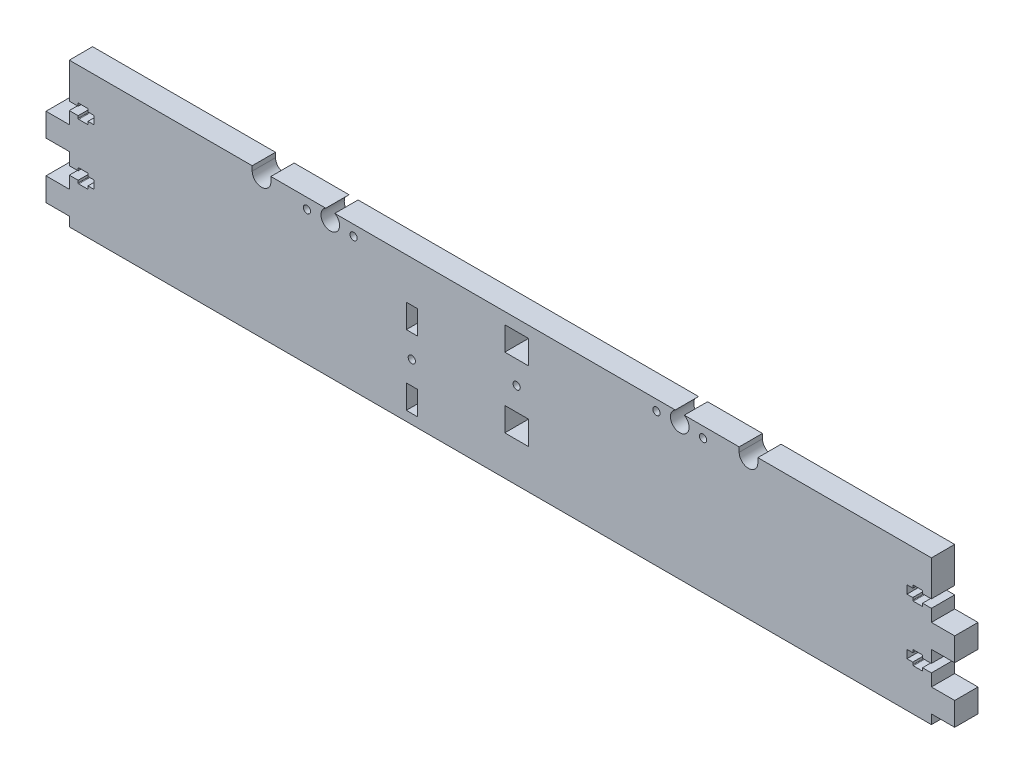
SolidWorks part; units mm, degrees
ref_plane "Front Plane" through (0, 0, 0) normal (0, 0, 1) x (1, 0, 0)
ref_plane "Top Plane" through (0, 0, 0) normal (0, 1, 0) x (1, 0, 0)
ref_plane "Right Plane" through (0, 0, 0) normal (1, 0, 0) x (0, 0, -1)
sketch "Sketch1" plane through (0, 0, 0) normal (0, 0, 1) x (1, 0, 0)
  line L0 (0, 0) -> (-185, 0)
  line L1 (-185, 0) -> (-185, -62) construction
  line L2 (0, -62) -> (-185, -62)
  line L3 (-185, -62) -> (-185, -58)
  line L4 (-185, -58) -> (-195, -58)
  line L5 (-195, -58) -> (-195, -48)
  line L6 (-195, -48) -> (-185, -48)
  line L7 (-185, -48) -> (-185, -34)
  line L8 (-185, -34) -> (-195, -34)
  line L9 (-195, -34) -> (-195, -24)
  line L10 (-195, -24) -> (-185, -24)
  line L11 (0, -62) -> (0, 0)
  line L12 (-185, -24) -> (-185, 0)
  line L13 (-195, -58) -> (-195, -24) construction
  line L14 (-195, -29) -> (-185, -29) construction
  line L15 (-195, -53) -> (-185, -53) construction
  dimension "D1" = 185
  dimension "D2" = 10
  dimension "D3" = 10
  dimension "D4" = 10
  dimension "D5" = 24
  dimension "D6" = 29
  dimension "D7" = 62
extrude "MainBody" add sketch "Sketch1" along normal blind 10
sketch "Sketch3" plane through (0, 0, 10) normal (0, 0, 1) x (1, 0, 0)
  line L0 (-185, -17) -> (-174.5, -17) construction
  line L1 (-185, 0) -> (-185, -24) construction
  line L2 (-185, -18.75) -> (-181.2, -18.75)
  line L3 (-181.2, -18.75) -> (-181.2, -19.75)
  line L4 (-180.95, -20) -> (-177.25, -20)
  line L5 (-177, -19.75) -> (-177, -18.75)
  line L6 (-177, -18.75) -> (-174.5, -18.75)
  line L7 (-174.5, -18.75) -> (-174.5, -15.25)
  line L8 (-181.2, -18.75) -> (-177, -18.75) construction
  line L9 (-195, -24) -> (-195, -34) construction
  line L10 (-181.2, -15.25) -> (-177, -15.25) construction
  line L11 (-177, -15.25) -> (-174.5, -15.25)
  line L12 (-177, -14.25) -> (-177, -15.25)
  line L13 (-180.95, -14) -> (-177.25, -14)
  line L14 (-181.2, -15.25) -> (-181.2, -14.25)
  line L15 (-185, -15.25) -> (-181.2, -15.25)
  line L16 (-185, -18.75) -> (-185, -15.25)
  line L17 (-185, -24) -> (-185, -34) construction
  line L19 (-195, -24) -> (-195, -34) construction
  line L20 (-195, -29) -> (-185, -29) construction
  line L21 (-181.2, -42.75) -> (-177, -42.75) construction
  line L22 (-181.2, -39.25) -> (-177, -39.25) construction
  line L23 (-185, -41) -> (-174.5, -41) construction
  line L24 (-185, -39.25) -> (-185, -42.75)
  line L25 (-185, -42.75) -> (-181.2, -42.75)
  line L26 (-181.2, -42.75) -> (-181.2, -43.75)
  line L27 (-180.95, -44) -> (-177.25, -44)
  line L28 (-177, -43.75) -> (-177, -42.75)
  line L29 (-177, -42.75) -> (-174.5, -42.75)
  line L30 (-174.5, -39.25) -> (-174.5, -42.75)
  line L31 (-177, -39.25) -> (-174.5, -39.25)
  line L32 (-177, -38.25) -> (-177, -39.25)
  line L33 (-180.95, -38) -> (-177.25, -38)
  line L34 (-181.2, -39.25) -> (-181.2, -38.25)
  line L35 (-185, -39.25) -> (-181.2, -39.25)
  line L36 (-181.2, -15.25) -> (-177, -15.25) construction
  arc A0 (-177.25, -20) -> (-177, -19.75) centre (-177.25, -19.75) ccw
  arc A1 (-181.2, -19.75) -> (-180.95, -20) centre (-180.95, -19.75) ccw
  arc A2 (-181.2, -14.25) -> (-180.95, -14) centre (-180.95, -14.25) cw
  arc A3 (-177.25, -14) -> (-177, -14.25) centre (-177.25, -14.25) cw
  arc A4 (-177.25, -44) -> (-177, -43.75) centre (-177.25, -43.75) ccw
  arc A5 (-181.2, -43.75) -> (-180.95, -44) centre (-180.95, -43.75) ccw
  arc A6 (-181.2, -38.25) -> (-180.95, -38) centre (-180.95, -38.25) cw
  arc A7 (-177.25, -38) -> (-177, -38.25) centre (-177.25, -38.25) cw
  point P6 (-195, -29)
  point P15 (-177, -20)
  point P18 (-181.2, -20)
  point P29 (-181.2, -14)
  point P30 (-177, -14)
  point P62 (-177, -44)
  point P63 (-181.2, -44)
  point P64 (-181.2, -38)
  point P65 (-177, -38)
  dimension "D2" = 8
  dimension "D7" = 0.25
  dimension "D1" = 10.5
  dimension "D3" = 1.75
  dimension "D4" = 3
  dimension "D5" = 12
  dimension "D6" = 4.2
extrude "ScrewCutouts" cut sketch "Sketch3" against normal through all
mirror "Mirror1" about plane through (0, 0, 0) normal (1, 0, 0) of "ScrewCutouts", "MainBody"
sketch "Sketch2" plane through (0, 0, 10) normal (0, 0, 1) x (1, 0, 0)
  line L0 (0, 0) -> (0, -62) construction
  line L1 (-185, -62) -> (185, -62) construction
  line L2 (2, 0) -> (2, -62) construction
  line L3 (185, 0) -> (-185, 0) construction
  line L4 (-63, -4.5) -> (-83, -4.5) construction
  line L5 (-73, -7.5) -> (-73, 0.5) construction
  line L6 (77, -7.5) -> (77, 0.5) construction
  line L7 (67, -4.5) -> (87, -4.5) construction
  circle A0 centre (-73, -3.5) radius 4
  circle A1 centre (-83, -4.5) radius 1.55
  circle A2 centre (-63, -4.5) radius 1.55
  circle A3 centre (67, -4.5) radius 1.55
  circle A4 centre (87, -4.5) radius 1.55
  circle A5 centre (77, -3.5) radius 4
  dimension "D1" = 3.1
  dimension "D2" = 8
  dimension "D4" = 3.5
  dimension "D5" = 75
  dimension "D6" = 2
  dimension "D3" = 10
  dimension "D7" = 1
extrude "RodCutouts" cut sketch "Sketch2" against normal through all
sketch "Sketch4" plane through (0, 0, 10) normal (0, 0, 1) x (1, 0, 0)
  line L0 (77, -3.5) -> (-73, -3.5) construction
  line L1 (2, -3.5) -> (2, -62) construction
  line L2 (-185, -62) -> (185, -62) construction
  line L3 (7, -45.1) -> (7, -4.9) construction
  line L4 (75.0635, 0) -> (-71.0635, 0) construction
  line L5 (7, -10) -> (7, -40) construction
  line L6 (1.9, -4.9) -> (12.1, -4.9)
  line L7 (1.9, -4.9) -> (1.9, -15.1)
  line L8 (1.9, -15.1) -> (12.1, -15.1)
  line L9 (12.1, -4.9) -> (12.1, -15.1)
  line L10 (1.9, -4.9) -> (12.1, -15.1) construction
  line L11 (1.9, -15.1) -> (12.1, -4.9) construction
  line L12 (1.9, -34.9) -> (12.1, -34.9)
  line L13 (1.9, -34.9) -> (1.9, -45.1)
  line L14 (1.9, -45.1) -> (12.1, -45.1)
  line L15 (12.1, -34.9) -> (12.1, -45.1)
  line L16 (1.9, -34.9) -> (12.1, -45.1) construction
  line L17 (1.9, -45.1) -> (12.1, -34.9) construction
  circle A0 centre (7, -25) radius 1.55
  point P12 (7, -10)
  point P17 (7, -40)
  dimension "D8" = 3.1
  dimension "D1" = 10.2
  dimension "D2" = 10.2
  dimension "D3" = 10.2
  dimension "D4" = 10.2
  dimension "D5" = 30
  dimension "D6" = 10
  dimension "D7" = 5
extrude "Cut-Extrude3" cut sketch "Sketch4" against normal through all
sketch "Sketch5" plane through (0, 0, 10) normal (0, 0, 1) x (1, 0, 0)
  line L0 (-38, 0) -> (-38, -62) construction
  line L1 (-74.9365, 0) -> (-185, 0) construction
  line L2 (-185, -62) -> (185, -62) construction
  line L3 (-40.35, -27.85) -> (-40.35, -47.65) construction
  line L4 (-40.35, -17.65) -> (-35.65, -17.65)
  line L5 (-40.35, -17.65) -> (-40.35, -27.85)
  line L6 (-40.35, -27.85) -> (-35.65, -27.85)
  line L7 (-35.65, -17.65) -> (-35.65, -27.85)
  line L8 (-40.35, -17.65) -> (-35.65, -27.85) construction
  line L9 (-40.35, -27.85) -> (-35.65, -17.65) construction
  line L10 (-40.35, -47.65) -> (-35.65, -47.65)
  line L11 (-40.35, -47.65) -> (-40.35, -57.85)
  line L12 (-40.35, -57.85) -> (-35.65, -57.85)
  line L13 (-35.65, -47.65) -> (-35.65, -57.85)
  line L14 (-40.35, -47.65) -> (-35.65, -57.85) construction
  line L15 (-40.35, -57.85) -> (-35.65, -47.65) construction
  line L16 (-35.65, -47.65) -> (-35.65, -27.85) construction
  line L17 (-40.35, -37.75) -> (-35.65, -37.75) construction
  line L18 (-73, -3.5) -> (77, -3.5) construction
  line L19 (2, -3.5) -> (2, -62) construction
  line L20 (2, -32.75) -> (-195, -32.75) construction
  line L21 (-195, -24) -> (-195, -34) construction
  line L22 (-31.45, 8.9944) -> (-31.45, 5) construction
  line L23 (75.0635, 0) -> (-71.0635, 0) construction
  line L24 (-28.25, 8.9944) -> (-28.25, 5)
  line L25 (-34.65, 8.9944) -> (-34.65, 5)
  circle A0 centre (-38, -37.75) radius 1.55
  arc A1 (-28.25, 8.9944) -> (-34.65, 8.9944) centre (-31.45, 8.9944) ccw
  arc A2 (-34.65, 5) -> (-28.25, 5) centre (-31.45, 5) ccw
  point P6 (-38, -22.75)
  point P11 (-38, -52.75)
  point P34 (-31.45, 6.9972)
  dimension "D3" = 10.2
  dimension "D4" = 10.2
  dimension "D5" = 30
  dimension "D6" = 3.1
  dimension "D9" = 3.2
  dimension "D1" = 4.7
  dimension "D2" = 0
  dimension "D7" = 40
  dimension "D8" = 5
  dimension "D10" = 5
  dimension "D11" = 1
extrude "EndstopHolder" cut sketch "Sketch5" against normal through all
sketch "Sketch6" plane through (0, 0, 10) normal (0, 0, 1) x (1, 0, 0)
  line L0 (-40.35, -47.65) -> (-40.35, -27.85) construction
  line L1 (-42.35, -47.65) -> (-27.65, -47.65) construction
  line L3 (-27.65, -53.65) -> (-27.65, -41.65) construction
  line L4 (-29.65, -53.65) -> (-29.65, -41.65)
  line L5 (-25.65, -53.65) -> (-25.65, -41.65)
  line L6 (-35.65, -47.65) -> (-40.35, -47.65) construction
  line L7 (-35.65, -57.85) -> (-35.65, -47.65) construction
  arc A0 (-29.65, -53.65) -> (-25.65, -53.65) centre (-27.65, -53.65) ccw
  arc A1 (-25.65, -41.65) -> (-29.65, -41.65) centre (-27.65, -41.65) ccw
  point P10 (-27.65, -47.65)
  dimension "D1" = 2
  dimension "D2" = 12
  dimension "D3" = 8
  dimension "D4" = 0
extrude "EndstopWires" [suppressed] cut sketch "Sketch6" against normal through all
sketch "Sketch7" plane through (0, 0, 10) normal (0, 0, 1) x (1, 0, 0)
  line L0 (-73, -3.5) -> (77, -3.5) construction
  line L1 (2, -3.5) -> (2, -62) construction
  line L3 (-102.5, 0) -> (-102.5, -2) construction
  line L4 (-74.9365, 0) -> (-185, 0) construction
  line L5 (-98.5, 0) -> (-98.5, -2)
  line L6 (-106.5, 0) -> (-106.5, -2)
  line L7 (106.5, 0) -> (106.5, -2) construction
  line L8 (102.5, 0) -> (102.5, -2)
  line L9 (110.5, 0) -> (110.5, -2)
  line L10 (-185, -62) -> (185, -62) construction
  arc A0 (-98.5, 0) -> (-106.5, 0) centre (-102.5, 0) ccw
  arc A1 (-106.5, -2) -> (-98.5, -2) centre (-102.5, -2) ccw
  arc A2 (102.5, 0) -> (110.5, 0) centre (106.5, 0) cw
  arc A3 (110.5, -2) -> (102.5, -2) centre (106.5, -2) cw
  point P12 (-102.5, -1)
  point P19 (106.5, -1)
  dimension "D3" = 4
  dimension "D1" = 2
  dimension "D2" = 104.5
extrude "Cut-Extrude4" cut sketch "Sketch7" against normal through all
equation "\"Y-ROD-SPACING\"=75"
equation "\"D5@Sketch2\"=\"Y-ROD-SPACING\""
equation "\"Y-BED-OFFSET\"=2"
equation "\"D6@Sketch2\"=\"Y-BED-OFFSET\""
equation "\"T-SLOT-NUT-FILLET-RADIUS\"=0.25"
equation "\"D7@Sketch3\"=\"T-SLOT-NUT-FILLET-RADIUS\""
equation "\"T-SLOT-SCREW-SHAFT-RADIUS\"=1.75"
equation "\"D3@Sketch3\"=\"T-SLOT-SCREW-SHAFT-RADIUS\""
equation "\"T-SLOT-SCREW-SHAFT-CUTOUT-LENGTH\"=10.5"
equation "\"D1@Sketch3\"=\"T-SLOT-SCREW-SHAFT-CUTOUT-LENGTH\""
equation "\"T-SLOT-NUT-DEPTH\"=4.2"
equation "\"D6@Sketch3\"=\"T-SLOT-NUT-DEPTH\""
equation "\"T-SLOT-NUT-WIDTH\"=3"
equation "\"D4@Sketch3\"=\"T-SLOT-NUT-WIDTH\""
equation "\"T-SLOT-NUT-END-DISTANCE\"=8"
equation "\"D2@Sketch3\"=\"T-SLOT-NUT-END-DISTANCE\""
equation "\"ACRYLIC-TAB-CUTOUT-SIZE\"=\"ACRYLIC-THICKNESS\"+\"ACRYLIC-TAB-TOLERANCE\"*2"
equation "\"D1@Sketch4\"=\"ACRYLIC-TAB-CUTOUT-SIZE\""
equation "\"D2@Sketch4\"=\"ACRYLIC-TAB-CUTOUT-SIZE\""
equation "\"D3@Sketch4\"=\"ACRYLIC-TAB-CUTOUT-SIZE\""
equation "\"D4@Sketch4\"=\"ACRYLIC-TAB-CUTOUT-SIZE\""
equation "\"ACRYLIC-M3-HOLE\"=3.1"
equation "\"D8@Sketch4\"=\"ACRYLIC-M3-HOLE\""
equation "\"Y-BED-ROD-INSET\"=3.5"
equation "\"D1@Sketch2\"=\"ACRYLIC-M3-HOLE\""
equation "\"D4@Sketch2\"=\"Y-BED-ROD-INSET\""
equation "\"SMOOTHROD-CAP-SCREW-DISTANCE\"=20"
equation "\"D3@Sketch2\"=\"SMOOTHROD-CAP-SCREW-DISTANCE\"/2"
equation "\"ACRYLIC-TAB-WIDTH\"=\"ACRYLIC-THICKNESS\""
equation "\"FRAME-WIDTH-INNER\"=370"
equation "\"D2@Sketch1\"=\"ACRYLIC-TAB-WIDTH\""
equation "\"D3@Sketch1\"=\"ACRYLIC-TAB-WIDTH\""
equation "\"D4@Sketch1\"=\"ACRYLIC-TAB-WIDTH\""
equation "\"D1@Sketch1\"=\"FRAME-WIDTH-INNER\"/2"
equation "\"X-ROD-SPACING\"=45"
equation "\"Z-ROD-SPACING\"=17.5"
equation "\"ACRYLIC-THICKNESS\"=10"
equation "\"ACRYLIC-THICKNESS2\"=4.5"
equation "\"NEMA17-HOLE-SPACING\"=31"
equation "\"NEMA17-CENTRAL-CUTOUT\"=22.5"
equation "\"Z-BRACKET-REACH\"=55"
equation "\"TOP-BRACKET-SPACING\"=40"
equation "\"SMOOTHROD-X-LENGTH\"=350"
equation "\"SMOOTHROD-Y-LENGTH\"=350"
equation "\"SMOOTHROD-Z-LENGTH\"=350"
equation "\"SMOOTHROD-TIGHTENING-HEADROOM\"=.25"
equation "\"LEADSCREW-Z-LENGTH\"=300"
equation "\"SCREW-LENGTH-FRAME\"=\"ACRYLIC-THICKNESS\" + 10"
equation "\"SCREW-HEAD-RADIUS\"=6"
equation "\"PRINTED-X-SMOOTHROD-DIAMETER\"=8.2"
equation "\"PRINTED-X-SMOOTHROD-CUTOUT\"=10"
equation "\"PRINTED-X-BASE-HEIGHT\"=10"
equation "\"PRINTED-LM8UU-CUTOUT-SIZE\"=15.25"
equation "\"PRINTED-LM8UU-CUTOUT-LENGTH\"=24.5"
equation "\"PRINTED-X-IDLER-HEIGHT\"=16"
equation "\"PSU-MOUNTING-WIDTH\"=95"
equation "\"PSU-MOUNTING-HEIGHT\"=177"
equation "\"D1@MainBody\"=\"ACRYLIC-THICKNESS\""
equation "\"D1@Sketch5\"=\"ACRYLIC-THICKNESS2\"+\"ACRYLIC-TAB-TOLERANCE\"*2"
equation "\"D3@Sketch5\"=\"ACRYLIC-TAB-CUTOUT-SIZE\""
equation "\"D4@Sketch5\"=\"ACRYLIC-TAB-CUTOUT-SIZE\""
equation "\"D6@Sketch5\"=\"ACRYLIC-M3-HOLE\""
equation "\"Y-BED-SCREW-SPACING\"=209"
equation "\"Y-BED-SCREW-CUTOUT-SLOT-HEIGHT\"=2"
equation "\"Z-ROD-INSET\"=16"
equation "\"Y-BELT-TO-ROD-DISTANCE\"=20"
equation "\"SPOOL-HOLDER-ROD-SPACING\"=150"
equation "\"D1@Sketch7\"=\"Y-BED-SCREW-CUTOUT-SLOT-HEIGHT\""
equation "\"D2@Sketch7\"=\"Y-BED-SCREW-SPACING\"/2"
equation "\"ACRYLIC-TAB-TOLERANCE\"=.1"
equation "\"SCREW-LENGTH-MOTOR\"=\"ACRYLIC-THICKNESS\" + 5"
equation "\"SCREW-LENGTH-EXTRUDER\"=28"
equation "\"ACRYLIC-X-CARRIAGE-WIDTH\"=55"
equation "\"ACRYLIC-X-CARRIAGE-HEIGHT\"=75"
equation "\"ACRYLIC-X-CARRIAGE-LM8UU-CUTOUT-WIDTH\"=24.25"
equation "\"ACRYLIC-X-CARRIAGE-SCREW-SPACING-X\"=15"
equation "\"ACRYLIC-X-CARRIAGE-SCREW-SPACING-Y\"=33"
equation "\"ACRYLIC-X-CARRIAGE-CENTER-TAB-SPACING\"=14"
equation "\"ACRYLIC-X-CARRIAGE-EXTRUDER-OFFSET\"=26"
equation "\"ACRYLIC-X-CARRIAGE-EXTRUDER-ANGLE\"=90"
equation "\"ACRYLIC-X-CARRIAGE-EXTRUDER-SHELF-DEPTH\"=\"ACRYLIC-X-CARRIAGE-EXTRUDER-OFFSET\" + 28"
equation "\"ACRYLIC-X-CARRIAGE-EXTRUDER-BRACE-SPACING\"=23"
equation "\"ACRYLIC-X-CARRIAGE-EXTRUDER-BRACE-TAB-OFFSET\"=20"
equation "\"ACRYLIC-X-CARRIAGE-EXTRUDER-BRACE-HEIGHT\"=35"
equation "\"ACRYLIC-X-CARRIAGE-EXTRUDER-BRACE-SCREW-SPACING\"=22"
equation "\"PRINTED-M3-HOLE\"=3.5"
equation "\"ACRYLIC-X-CARRIAGE-LM8UU-CUTOUT-HEIGHT\"=11.5"
equation "\"ACRYLIC-X-CARRIAGE-DUAL-WIDTH-MULTIPLIER\"=1.65"
equation "\"ACRYLIC-X-CARRIAGE-DUAL-HOTEND-SPACING\"=42"
equation "\"ACRYLIC-X-CARRIAGE-DUAL-WIDTH\"=75"
equation "\"ACRYLIC-X-CARRIAGE-DUAL-HOTEND-SEPARATION\"=36"
equation "\"ACRYLIC-X-CARRIAGE-DUAL-MOUNT-PLATE-DEPTH\"=75"
equation "\"ACRYLIC-X-CARRIAGE-DUAL-MOUNT-BRACE-WIDTH\"=33"
equation "\"ACRYLIC-X-CARRIAGE-DUAL-MOUNT-SCREW-WIDTH\"=40"
equation "\"BLOWER-FAN-WIDTH\"=15"
